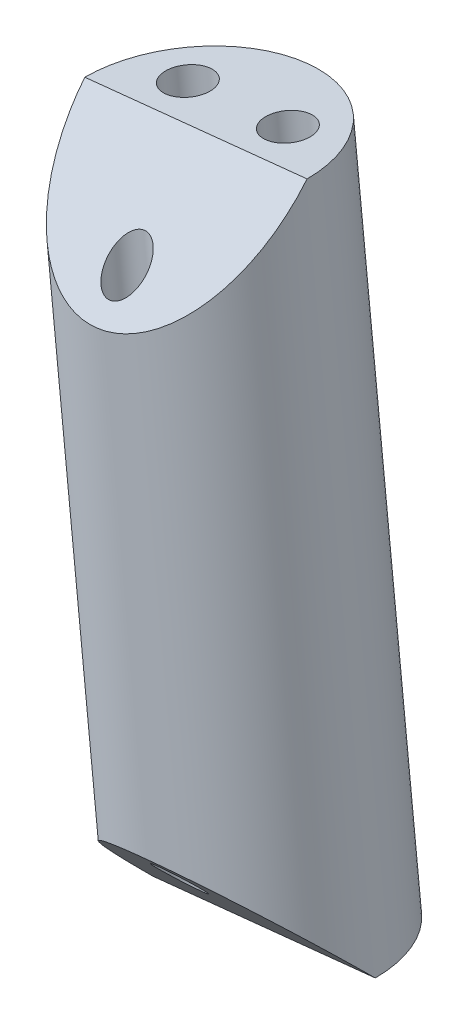
SolidWorks part; units mm, degrees
ref_plane "Front Plane" through (0, 0, 0) normal (0, 0, 1) x (1, 0, 0)
ref_plane "Top Plane" through (0, 0, 0) normal (0, 1, 0) x (1, 0, 0)
ref_plane "Right Plane" through (0, 0, 0) normal (1, 0, 0) x (0, 0, -1)
sketch "Sketch2" plane through (0, 0, 0) normal (0, 0, 1) x (1, 0, 0)
  line L0 (0, 0) -> (90, 0)
  line L1 (90, 0) -> (90, 120)
  line L2 (90, 120) -> (0, 120)
  line L3 (0, 120) -> (0, 0)
  line L4 (0, 120) -> (-10, 120)
  line L5 (-10, 120) -> (-10, 16.9491)
  line L6 (-10, 120) -> (57.5, 127)
  line L7 (57.5, 127) -> (90, 124)
  line L8 (90, 120) -> (99, 60)
  line L10 (90, 124) -> (90, 120)
  line L11 (5.9147, 0) -> (5.9147, -25)
  line L12 (5.9147, -25) -> (-4.0853, -25)
  line L13 (-4.0853, -29) -> (-4.0853, 0)
  line L14 (80, 0) -> (80, -25)
  line L15 (80, -25) -> (90, -25)
  line L16 (90, -29) -> (90, 0)
  line L17 (15.7927, 122.6748) -> (5.4776, 222.1414)
  line L18 (5.4776, 222.1414) -> (21.3923, 223.7918)
  line L19 (21.3923, 223.7918) -> (31.7073, 124.3252)
  line L20 (7.6492, 201.201) -> (23.5639, 202.8514)
  line L21 (10.9066, 169.7905) -> (26.8212, 171.441)
  line L22 (-10, 120) -> (-20.0396, 216.8108)
  line L23 (-20.0396, 216.8108) -> (-4.125, 218.4612)
  line L24 (-4.125, 218.4612) -> (5.9147, 121.6504)
  line L25 (-17.926, 196.4296) -> (-2.0114, 198.08)
  line L26 (-14.7556, 165.8578) -> (1.159, 167.5082)
  line L27 (57.5, 127) -> (46.9095, 229.1223)
  line L28 (46.9095, 229.1223) -> (30.9949, 227.4719)
  line L29 (30.9949, 227.4719) -> (41.5853, 125.3496)
  line L30 (33.2245, 205.9725) -> (49.1391, 207.6229)
  line L31 (36.5688, 173.7233) -> (52.4835, 175.3737)
  line L34 (90, 124) -> (99.1917, 223.5767)
  line L35 (99.1917, 223.5767) -> (83.2594, 225.0473)
  line L36 (83.2594, 225.0473) -> (74.0677, 125.4707)
  line L38 (81.3243, 204.0838) -> (97.2566, 202.6132)
  line L39 (78.4217, 172.6386) -> (94.354, 171.1679)
  line L40 (62.4078, 79.6749) -> (57.5, 127) construction
  line L41 (41.5853, 125.3496) -> (46.4931, 78.0244) construction
  line L42 (46.4931, 78.0244) -> (62.4078, 79.6749) construction
  line L43 (31.7073, 124.3252) -> (36.6151, 77.0001) construction
  line L44 (36.6151, 77.0001) -> (20.7005, 75.3496) construction
  line L45 (20.7005, 75.3496) -> (15.7927, 122.6748) construction
  line L46 (5.9147, 121.6504) -> (10.8224, 74.3253) construction
  line L47 (10.8224, 74.3253) -> (-5.0922, 72.6749) construction
  line L48 (-5.0922, 72.6749) -> (-10, 120) construction
  line L49 (74.0677, 125.4707) -> (69.6944, 78.0931) construction
  line L50 (69.6944, 78.0931) -> (85.7624, 78.0931) construction
  line L51 (85.7624, 78.0931) -> (90, 124) construction
  line L52 (-12.0823, 217.636) -> (10.4873, 0) construction
  line L53 (13.4349, 222.9666) -> (36.5574, 0) construction
  line L54 (38.9522, 228.2971) -> (62.6275, 0) construction
  line L55 (91.2256, 224.312) -> (70.5198, 0) construction
  line L59 (99, 60) -> (93.5277, 44.9649)
  line L60 (99, 60) -> (169.4769, 34.3485)
  line L61 (169.4769, 34.3485) -> (164.0046, 19.3134)
  line L62 (164.0046, 19.3134) -> (93.5277, 44.9649)
  line L63 (90, -2) -> (100, -2)
  line L64 (141.2862, 44.6091) -> (135.8138, 29.574)
  line L65 (99, 60) -> (55.7741, 75.7329) construction
  line L66 (55.7741, 75.7329) -> (50.3018, 60.6978) construction
  line L67 (100, -2) -> (100, -29)
  line L70 (-4.0853, -2) -> (-14.0853, -2)
  line L71 (-14.0853, -2) -> (-14.0853, -29)
  line L74 (-4.0853, 0) -> (0, 0)
  line L75 (-14.0853, -29) -> (-14.0853, -112.587)
  line L76 (-14.0853, -112.587) -> (100, -112.587)
  line L77 (100, -112.587) -> (100, -29)
  line L78 (-14.0853, -29) -> (100, -29)
  line L79 (-14.0853, -14.5) -> (100, -14.5) construction
  line L80 (31.7073, -112.587) -> (31.7073, -122.6232)
  line L81 (31.7073, -122.6232) -> (42.9573, -122.6232)
  line L82 (42.9573, -122.6232) -> (42.9573, -112.587)
  line L83 (-14.0853, -112.587) -> (-88.3667, -112.587)
  line L84 (-88.3667, -112.587) -> (-88.3667, -128.2699)
  line L85 (-88.3667, -128.2699) -> (169.4958, -128.2699)
  line L86 (169.4958, -128.2699) -> (169.4958, -112.587)
  line L87 (169.4958, -112.587) -> (100, -112.587)
  line L88 (90, 60) -> (-10, 60) construction
  line L89 (50.3018, 60.6978) -> (93.5277, 44.9649) construction
  line L90 (87.2806, 55.7521) -> (166.7408, 26.8309) construction
  line L91 (87.2806, 55.7521) -> (82.1749, 52.5336) construction
  line L92 (82.1749, 52.5336) -> (77.3257, 0) construction
  line L93 (83.1185, 56.6957) -> (86.337, 51.59) construction
  arc A0 (-10, 16.9491) -> (-4.0853, 0) centre (14.9876, 16.1624) ccw
  arc A1 (93.5277, 44.9649) -> (90, 0) centre (-126.4069, 39.5988) cw
  point P42 (41.1818, 206.7977)
  point P100 (84.7278, 54.1428)
  point P101 (84.7278, 54.1428)
  dimension "D11" = 47.3684
  dimension "D35" = 9
  dimension "D32" = 220
  dimension "D36" = 25
  dimension "D1" = 120
  dimension "D2" = 90
  dimension "D3" = 10
  dimension "D5" = 67.862
  dimension "D6" = 7
  dimension "D7" = 4
  dimension "D8" = 16
  dimension "D9" = 16
  dimension "D10" = 100
  dimension "D12" = 31.5789
  dimension "D13" = 16
  dimension "D14" = 16
  dimension "D15" = 16
  dimension "D16" = 25.7927
  dimension "D17" = 100
  dimension "D18" = 21.0526
  dimension "D19" = 31.5789
  dimension "D20" = 97.33
  dimension "D21" = 102.67
  dimension "D22" = 20.4905
  dimension "D23" = 30.7358
  dimension "D24" = 21.6147
  dimension "D25" = 32.4221
  dimension "D26" = 25
  dimension "D28" = 25
  dimension "D29" = 75
  dimension "D30" = 47.5789
  dimension "D31" = 30
  dimension "D33" = 46
  dimension "D34" = 20
  dimension "D37" = 2
  dimension "D38" = 2
  dimension "D39" = 27
  dimension "D40" = 10
  dimension "D41" = 10
  dimension "D42" = 27
  dimension "D43" = 14.5
  dimension "D44" = 127.5
ref_plane "Plane1" through (87.2806, 55.7521, 0) normal (-0.846, -0.5333, 0) x (0, 0, 1)
ref_plane "Plane2" through (82.1749, 52.5336, 0) normal (-0.0919, -0.9958, 0) x (-0.9958, 0.0919, 0)
ref_plane "Plane3" through (91.2256, 224.312, 0) normal (-0.0919, -0.9958, 0) x (-0.9958, 0.0919, 0)
ref_plane "Plane4" through (38.9522, 228.2971, 0) normal (0.1032, -0.9947, 0) x (-0.9947, -0.1032, 0)
ref_plane "Plane5" through (13.4349, 222.9666, 0) normal (0.1032, -0.9947, 0) x (-0.9947, -0.1032, 0)
ref_plane "Plane7" through (166.7408, 26.8309, 0) normal (0.9397, -0.342, 0) x (0, 0, -1)
ref_plane "Plane8" through (110.4217, -40.1902, 0) normal (0.9397, -0.342, 0) x (0, 0, -1)
ref_plane "Plane9" through (19.3664, 209.803, 0) normal (-0.0919, -0.9958, 0) x (-0.9958, 0.0919, 0)
ref_plane "Plane10" through (16.4638, 178.3578, 0) normal (-0.0919, -0.9958, 0) x (-0.9958, 0.0919, 0)
ref_plane "Plane11" through (-20.7793, 200.3721, 0) normal (0.1032, -0.9947, 0) x (-0.9947, -0.1032, 0)
ref_plane "Plane12" through (-17.435, 168.1229, 0) normal (0.1032, -0.9947, 0) x (-0.9947, -0.1032, 0)
ref_plane "Plane13" through (-20.5619, 198.2754, 0) normal (0.1032, -0.9947, 0) x (-0.9947, -0.1032, 0)
ref_plane "Plane14" through (-17.3045, 166.8649, 0) normal (0.1032, -0.9947, 0) x (-0.9947, -0.1032, 0)
ref_plane "Plane15" through (-12.0823, 217.636, 0) normal (0.1032, -0.9947, 0) x (-0.9947, -0.1032, 0)
ref_plane "Plane16" through (-20.3445, 196.1788, 0) normal (0.1032, -0.9947, 0) x (-0.9947, -0.1032, 0)
ref_plane "Plane17" through (-17.1741, 165.607, 0) normal (0.1032, -0.9947, 0) x (-0.9947, -0.1032, 0)
ref_plane "Plane18" through (12.1098, 131.1899, 0) normal (-0.0919, -0.9958, 0) x (-0.9958, 0.0919, 0)
ref_plane "Plane19" through (-12.4184, 119.7492, 0) normal (0.1032, -0.9947, 0) x (-0.9947, -0.1032, 0)
ref_plane "Plane20" through (0, 0, 0) normal (0, 0, 1) x (0.1032, -0.9947, 0)
ref_plane "Plane21" through (0, 0, 0) normal (0, 0, 1) x (-0.0919, -0.9958, 0)
ref_plane "Plane22" through (10.3758, 1.076, 0) normal (-0.9947, -0.1032, 0) x (0.1032, -0.9947, 0)
ref_plane "Plane23" through (36.1684, 3.7508, 0) normal (-0.9947, -0.1032, 0) x (0.1032, -0.9947, 0)
ref_plane "Plane24" through (61.9611, 6.4256, 0) normal (-0.9947, -0.1032, 0) x (0.1032, -0.9947, 0)
ref_plane "Plane25" through (69.924, -6.4545, 0) normal (-0.9958, 0.0919, 0) x (-0.0919, -0.9958, 0)
sketch "Sketch3" plane through (-20.3445, 196.1788, 0) normal (0.1032, -0.9947, 0) x (-0.9947, -0.1032, 0)
  line L0 (-2.4314, 0) -> (-18.4314, 0) construction
  circle A0 centre (-10.4314, 0) radius 8
  dimension "D1" = 16
extrude "Boss-Extrude1" add sketch "Sketch3" along normal blind 47.3684
sketch "Sketch4" plane through (10.3758, 1.076, 0) normal (-0.9947, -0.1032, 0) x (0.1032, -0.9947, 0)
  line L0 (-197.2309, 0) -> (-189.2309, 8)
  line L1 (-197.2309, 8) -> (-197.2309, -8) construction
  line L2 (-149.8624, 8) -> (-197.2309, 8) construction
  line L3 (-189.2309, 8) -> (-197.2309, 8)
  line L4 (-197.2309, 8) -> (-197.2309, 0)
  line L5 (-157.8624, 8) -> (-149.8624, 8)
  line L6 (-149.8624, 8) -> (-149.8624, 0)
  line L7 (-217.7214, 0) -> (1.0818, 0) construction
  line L8 (-149.8624, 0) -> (-157.8624, 8)
  dimension "D1" = 45
  dimension "D2" = 45
extrude "Cut-Extrude1" cut sketch "Sketch4" against normal through all and the other way through all
sketch "Sketch5" plane through (10.3758, 1.076, 0) normal (-0.9947, -0.1032, 0) x (0.1032, -0.9947, 0)
  line L0 (-149.8624, 0) -> (-153.8624, 4)
  line L1 (-149.8624, 0) -> (-157.8624, 8) construction
  line L2 (-153.8624, 4) -> (-145.8624, 4)
  line L3 (-145.8624, 4) -> (-145.8624, 0)
  line L4 (-213.7055, 0) -> (7.2742, 0) construction
  line L6 (-149.8624, 0) -> (-145.8624, 4) construction
  line L7 (-145.8624, 0) -> (-149.8624, -4)
  line L8 (-149.8624, -8) -> (-149.8624, 0) construction
  line L9 (-149.8624, 0) -> (-149.8624, -4)
  dimension "D1" = 4
  dimension "D2" = 45
sketch "Sketch7" plane through (10.3758, 1.076, 0) normal (-0.9947, -0.1032, 0) x (0.1032, -0.9947, 0)
  line L0 (-193.2309, 4) -> (-197.2309, 0)
  line L1 (-217.7214, 0) -> (1.0818, 0) construction
  line L4 (-197.2309, -4) -> (-197.2309, 0)
  line L5 (-193.2309, 4) -> (-193.2309, 0)
  arc A0 (-197.2309, -4) -> (-193.2309, 0) centre (-197.2309, 0) ccw
  dimension "D1" = 4
  dimension "D2" = 4
sketch "Sketch8" plane through (-20.3445, 196.1788, 0) normal (-0.1032, 0.9947, 0) x (0.9947, 0.1032, 0)
  line L0 (2.4314, 0) -> (18.4314, 0) construction
  circle A0 centre (10.4314, -5.5) radius 1.4
  circle A1 centre (6.8314, 3) radius 1.6
  circle A2 centre (14.0314, 3) radius 1.6
  point P9 (10.4314, 0)
  dimension "D1" = 3.2
  dimension "D2" = 3.2
  dimension "D3" = 2.8
  dimension "D4" = 3
  dimension "D5" = 5.5
  dimension "D6" = 3.6
  dimension "D7" = 3.6
  dimension "D8" = 3
extrude "Cut-Extrude3" cut sketch "Sketch8" against normal through all and the other way through all
sketch "Sketch9" plane through (-20.3445, 196.1788, 0) normal (-0.1032, 0.9947, 0) x (0.9947, 0.1032, 0)
  line L0 (4.5289, 5.4) -> (16.3339, 5.4)
  line L1 (-101.1265, 0) -> (155.3606, 0) construction
  arc A0 (18.4314, 0) -> (2.4314, 0) centre (10.4314, 0) ccw construction
  arc A1 (4.5289, 5.4) -> (16.3339, 5.4) centre (10.4314, 0) cw
  dimension "D1" = 5.4
